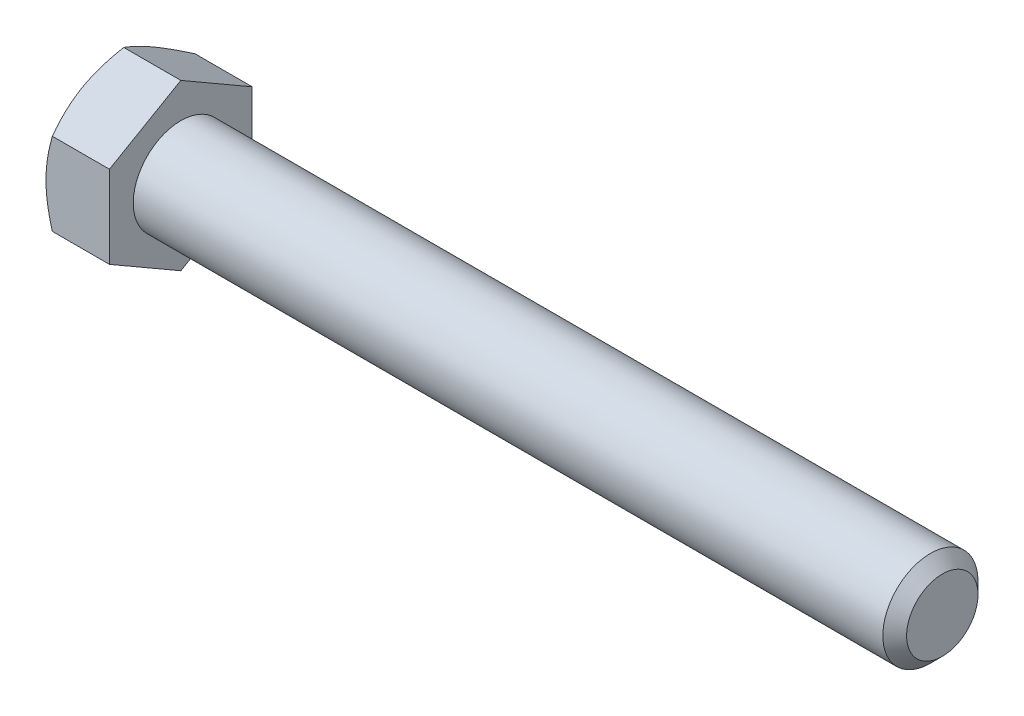
SolidWorks part; units mm, degrees
material "Alloy Steel"
ref_plane "Front Plane" through (0, 0, 0) normal (0, 0, 1) x (1, 0, 0)
ref_plane "Top Plane" through (0, 0, 0) normal (0, 1, 0) x (1, 0, 0)
ref_plane "Right Plane" through (0, 0, 0) normal (1, 0, 0) x (0, 0, -1)
sketch "Sketch1" plane through (0, 0, 0) normal (0, 0, 1) x (1, 0, 0)
  line L0 (-41.275, 0) -> (41.275, 0) construction
  line L1 (41.275, 4.7625) -> (41.275, -4.7625) construction
  line L2 (-34.925, 7.1437) -> (-34.925, -7.1437) construction
  line L3 (-41.275, 7.1437) -> (-41.275, -7.1437) construction
  point P9 (-34.925, 0)
  point P10 (35.7188, -4.7625)
  dimension "Screw Dia" = 9.525
  dimension "Hex" = 14.2875
  dimension "Head Ht" = 6.35
  dimension "Screw Lenght" = 76.2
  dimension "D1" = 5.5562
ref_plane "Plane2" through (41.275, 0, 0) normal (1, 0, 0) x (0, 0, -1)
sketch "Sketch5" plane through (41.275, 0, 0) normal (1, 0, 0) x (0, 0, -1)
  circle A0 centre (0, 0) radius 4.7625
extrude "Boss-Extrude3" add sketch "Sketch5" against normal up to vertex (76.2 mm away) up to point (-34.925, 0, 0)
sketch "Sketch9" plane through (41.275, 0, 0) normal (1, 0, 0) x (0, 0, -1)
  circle A1 centre (0, 0) radius 4.7625
  circle A2 centre (0, 0) radius 4.7625
  dimension "D1" = 0
curve "Helix/Spiral1" pitch 1.5875 height 26.9875 turns 17 parameters "Pitch"=1.5875
chamfer "Chamfer1" distance 1.1906 angle 45 1 edges at (41.275, 0, -4.7625)
sketch "Sketch10" plane through (0, 0, 0) normal (0, 0, 1) x (1, 0, 0)
  line L0 (41.275, 4.7625) -> (41.8703, 3.7314)
  line L1 (41.8703, 3.7314) -> (42.0687, 3.7314)
  line L2 (42.0687, 3.7314) -> (42.6641, 4.7625)
  line L3 (41.275, 4.7625) -> (42.6641, 4.7625)
  line L4 (41.9695, 4.7625) -> (41.9695, 3.7314) construction
  line L5 (41.5727, 4.2469) -> (42.3664, 4.2469) construction
  dimension "D1" = 60
  dimension "D2" = 0.1984
  dimension "D3" = 0.7937
sweep "Cut-Sweep1" [suppressed] cut profiles "Sketch10" path "Helix/Spiral1"
sketch "Sketch11" plane through (0, 0, 0) normal (0, 0, 1) x (1, 0, 0)
  line L0 (-34.925, 4.7625) -> (-34.925, 0)
  line L1 (-34.925, 0) -> (20.6375, 0)
  line L3 (20.6375, 0) -> (15.875, 4.7625)
  line L4 (-34.925, 4.7625) -> (15.875, 4.7625)
  dimension "D1" = 45
  dimension "MIn Thread" = 25.4
revolve "Revolve1" add sketch "Sketch11" angle 360 about L1
sketch "Sketch6" plane through (-34.925, 0, 0) normal (-1, 0, 0) x (0, 0, 1)
  line L0 (0, 7.1437) -> (0, -7.1437) construction
  line L1 (7.1438, 4.1244) -> (0, 8.2489)
  line L2 (0, 8.2489) -> (-7.1437, 4.1244)
  line L3 (-7.1437, 4.1244) -> (-7.1437, -4.1244)
  line L4 (-7.1437, -4.1244) -> (0, -8.2489)
  line L5 (0, -8.2489) -> (7.1438, -4.1244)
  line L6 (7.1438, -4.1244) -> (7.1438, 4.1244)
  circle A0 centre (0, 0) radius 7.1437 construction
extrude "Boss-Extrude4" add sketch "Sketch6" along normal up to vertex (6.35 mm away) up to point (-41.275, -7.1437, 0)
sketch "Sketch7" plane through (-41.275, 0, 0) normal (-1, 0, 0) x (0, 0, 1)
  circle A0 centre (0, 0) radius 7.1437 construction
  circle A1 centre (0, 0) radius 7.1437
sketch "Sketch8" plane through (-41.275, 0, 0) normal (-1, 0, 0) x (0, 0, 1)
  circle A0 centre (0, 0) radius 7.1437 construction
  circle A1 centre (0, 0) radius 7.1437
extrude "Cut-Extrude3" cut sketch "Sketch8" against normal through all draft 60 flip side to cut
sketch "Sketch12" plane through (-41.275, 0, 0) normal (-1, 0, 0) x (0, 0, 1)
  line L0 (0, 5.5007) -> (0, 3.0718) construction
  line L1 (0.2143, 5.5007) -> (0.2143, 3.0718)
  line L2 (-0.2143, 5.5007) -> (-0.2143, 3.0718)
  line L3 (0, 4.7625) -> (0, -4.7625) construction
  arc A0 (0.2143, 5.5007) -> (-0.2143, 5.5007) centre (0, 5.5007) ccw
  arc A1 (-0.2143, 3.0718) -> (0.2143, 3.0718) centre (0, 3.0718) ccw
  circle A3 centre (0, 0) radius 2.8575 construction
  circle A4 centre (0, 0) radius 5.715 construction
  point P2 (0, 4.2862)
  dimension "D1" = 5.715
  dimension "D3" = 11.43
  dimension "D2" = 0.4286
extrude "Cut-Extrude4" [suppressed] cut sketch "Sketch12" against normal blind 0.254
pattern_circular "CirPattern1" [suppressed] count 6 over 360 of bodies 116
equation "\"D2@Sketch10\" = \"Pitch@Helix/Spiral1\"*.125"
equation "\"D3@Sketch10\" = \"Pitch@Helix/Spiral1\"*.5"
equation "\"D3@Helix/Spiral1\" = \"MIn Thread@Sketch11\"+\"Pitch@Helix/Spiral1\""
equation "\"D1@Chamfer1\" = \"Pitch@Helix/Spiral1\"*.75"
equation "\"D1@Sketch12\" = \"Hex@Sketch1\"*.4"
equation "\"D3@Sketch12\" = \"Hex@Sketch1\"*.8"
equation "\"D2@Sketch12\" = \"Hex@Sketch1\"*.03"
equation "\"D1@Sketch1\" = \"Pitch@Helix/Spiral1\"*3.5"
